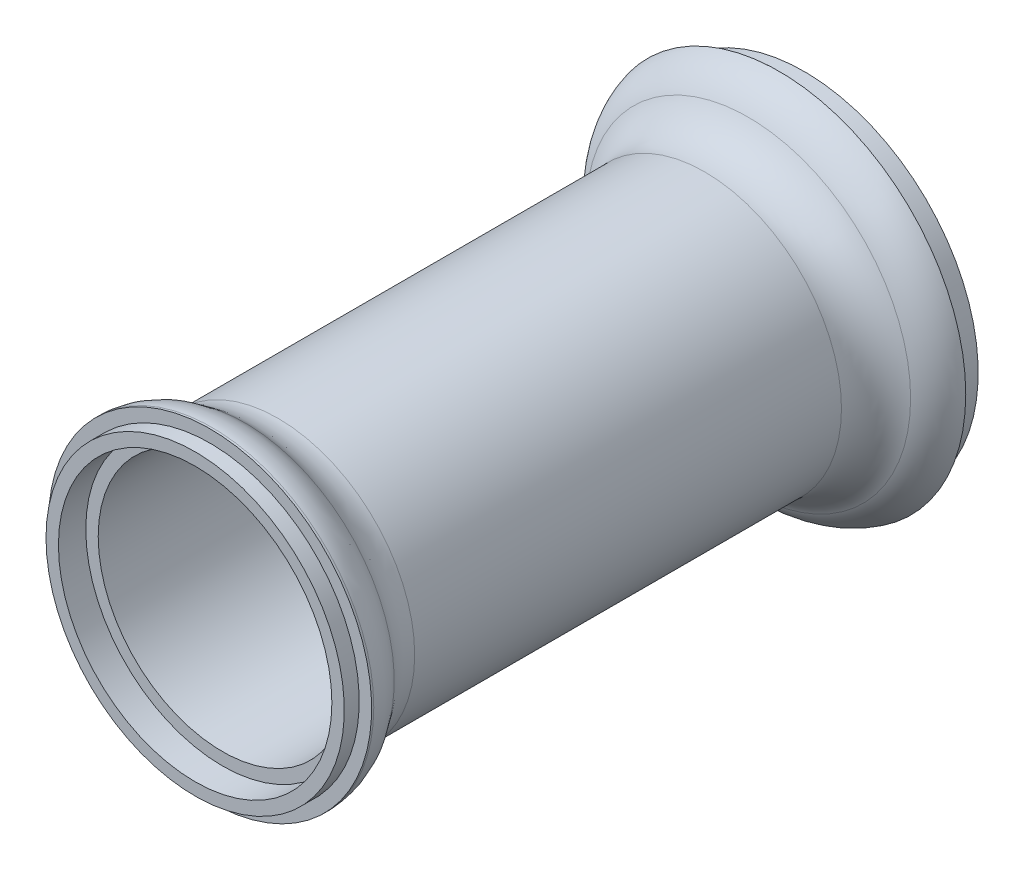
SolidWorks part; units mm, degrees
ref_plane "Front Plane" through (0, 0, 0) normal (0, 0, 1) x (1, 0, 0)
ref_plane "Top Plane" through (0, 0, 0) normal (0, 1, 0) x (1, 0, 0)
ref_plane "Right Plane" through (0, 0, 0) normal (1, 0, 0) x (0, 0, -1)
sketch "Sketch1" plane through (0, 0, 0) normal (0, 1, 0) x (1, 0, 0)
  line L0 (0, 0) -> (0, -122.5)
  line L1 (0, -122.5) -> (30, -122.5)
  line L2 (30, -122.5) -> (30, -119.5)
  line L3 (30, -119.5) -> (32.5, -119.5)
  line L4 (32.5, -119.5) -> (32.5, -114.5)
  line L5 (32.5, -114.5) -> (27.5, -114.5)
  line L6 (27.5, -114.5) -> (27.5, -10)
  line L7 (27.5, -10) -> (37.5, -10)
  line L8 (37.5, -10) -> (37.5, -5)
  line L9 (37.5, -5) -> (35, -5)
  line L10 (35, -5) -> (35, 0)
  line L11 (35, 0) -> (0, 0)
  dimension "D1" = 35
  dimension "D2" = 5
  dimension "D3" = 2.5
  dimension "D4" = 5
  dimension "D5" = 27.5
  dimension "D6" = 5
  dimension "D7" = 5
  dimension "D8" = 2.5
  dimension "D9" = 3
  dimension "D10" = 122.5
revolve "Revolve1" add sketch "Sketch1" angle 360 about L0
shell "Shell1" thickness 2.5 removed face at (-35, 0, 0) removed face at (-30, 0, 122.5)
fillet "Fillet1" radius 10 2 edges at (-27.5, 0, 10) (-27.5, 0, 114.5)
fillet "Fillet2" radius 10 2 edges at (-32.5, 0, 114.5) (-37.5, 0, 10)
